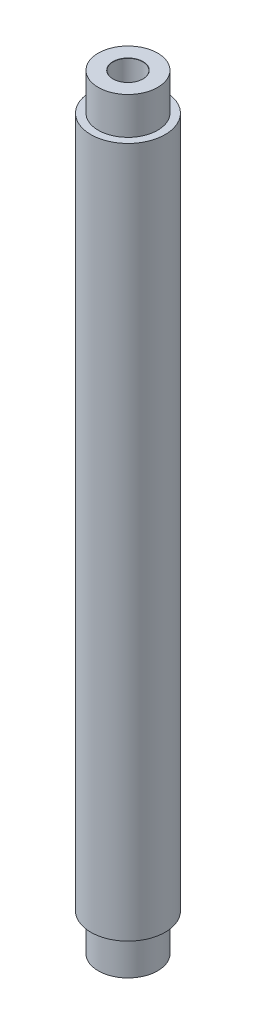
SolidWorks part; units mm, degrees
material "6061-T4 (SS)"
ref_plane "Front Plane" through (0, 0, 0) normal (0, 0, 1) x (1, 0, 0)
ref_plane "Top Plane" through (0, 0, 0) normal (0, 1, 0) x (1, 0, 0)
ref_plane "Right Plane" through (0, 0, 0) normal (1, 0, 0) x (0, 0, -1)
sketch "Sketch1" plane through (0, 0, 0) normal (0, 1, 0) x (1, 0, 0)
  circle A0 centre (0, 0) radius 5
  dimension "D1" = 10
extrude "Boss-Extrude1" add sketch "Sketch1" along normal blind 103
hole_wizard "Ø4.0mm Dowel Hole1" positions "3DSketch1" profile "Sketch4" hole size "Ø4.0" standard "ANSI Metric"
sketch3d "3DSketch1"
  line L0 (0, 103, 0) -> (0, 0, 0) construction
  point P0 (0, 103, 0)
  point P5 (0, 0, 0)
sketch "Sketch4" plane through (0, 103, 0) normal (1, 0, 0) x (0, 0, 1)
  line L0 (0, 0) -> (0, 19.2017)
  line L1 (0, 19.2017) -> (2, 18)
  line L2 (2, 18) -> (2, 0.025)
  line L3 (2, 0.025) -> (2.025, 0)
  line L5 (2.025, 0) -> (0, 0)
  line L6 (-2, 0.025) -> (-2.025, 0) construction
  line L10 (0, 19.2017) -> (-2, 18) construction
  line L11 (0, -6.35) -> (0, 107.95) construction
  dimension "Hole Dia." = 4
  dimension "Hole Depth" = 18
  dimension "Near C'Sink Dia." = 4.05
  dimension "Near C'Sink Angle" = 90
  dimension "Drill Angle" = 118
cosmetic thread "Cosmetic Thread1" parameters "D1"=10, "D2"=5
ref_plane "Plane3" through (0, 51.5, 0) normal (0, 1, 0) x (1, 0, 0)
mirror "Mirror1" about plane through (0, 51.5, 0) normal (0, 1, 0) of "Ø4.0mm Dowel Hole1"
cosmetic thread "Cosmetic Thread2" parameters "D1"=10, "D2"=5
sketch "Sketch5" plane through (0, 0, 0) normal (0, 0, 1) x (1, 0, 0)
  line L0 (0, 51.5) -> (-5, 51.5) construction
  line L1 (-5, 103) -> (-4, 103)
  line L2 (-5, 103) -> (-5, 98)
  line L3 (-5, 98) -> (-4, 98)
  line L4 (-4, 103) -> (-4, 98)
  line L9 (4.4, 51.5) -> (-4.4, 51.5) construction
  line L10 (-5, 103) -> (-5, 0) construction
  line L11 (-4, 0) -> (-4, 5)
  line L12 (-5, 5) -> (-4, 5)
  line L13 (-5, 0) -> (-5, 5)
  line L14 (-5, 0) -> (-4, 0)
  line L15 (0, 103) -> (0, 0) construction
  line L16 (5, 103) -> (-5, 103) construction
  dimension "D1" = 4
  dimension "D2" = 5
revolve "Cut-Revolve2" cut sketch "Sketch5" angle 360 about L15
equation "\"D1@Boss-Extrude1\"=103"
